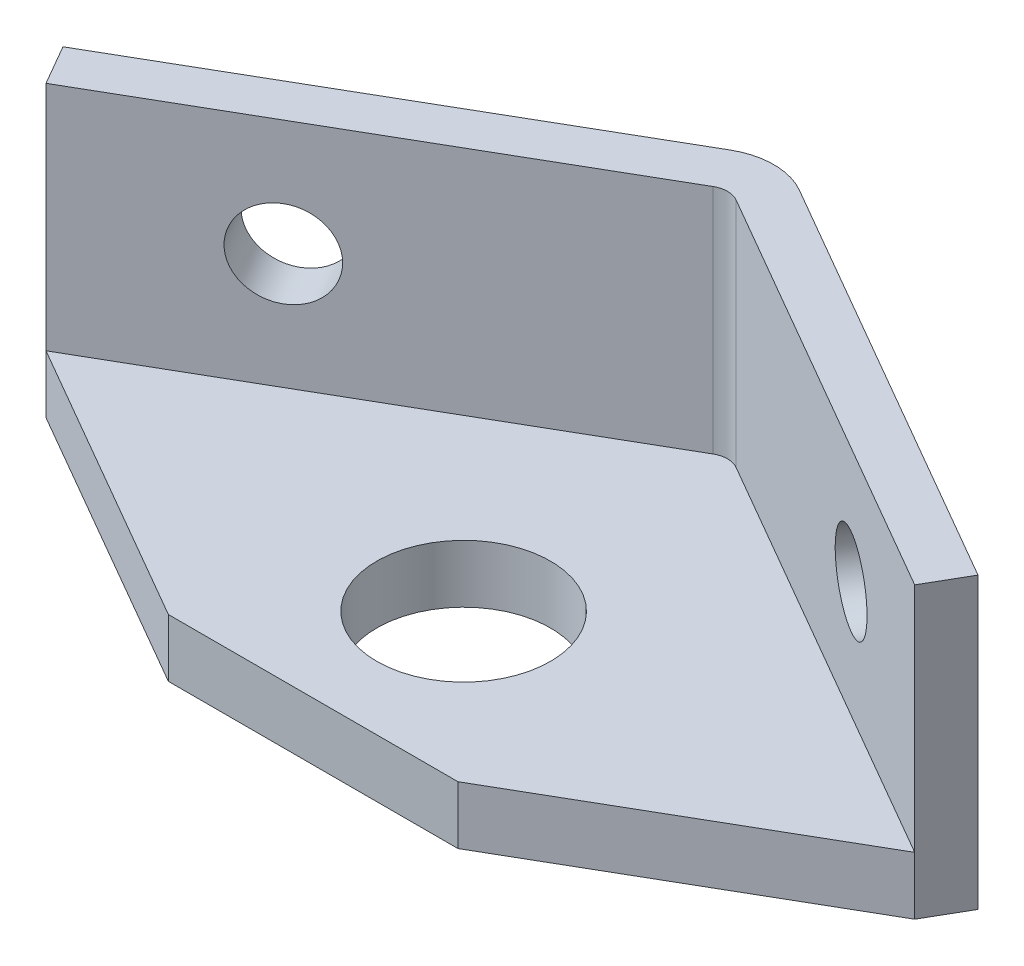
SolidWorks part; units mm, degrees
ref_plane "Plano frontal" through (0, 0, 0) normal (0, 0, 1) x (1, 0, 0)
ref_plane "Plano superior" through (0, 0, 0) normal (0, 1, 0) x (1, 0, 0)
ref_plane "Plano direito" through (0, 0, 0) normal (1, 0, 0) x (0, 0, -1)
sketch "Esboço1" plane through (0, 0, 0) normal (0, 1, 0) x (1, 0, 0)
  line L26 (-2, 45.0333) -> (-75, 2.8868)
  line L27 (-75, 2.8868) -> (0, -40.4145)
  line L28 (0, -40.4145) -> (75, 2.8868)
  line L29 (75, 2.8868) -> (2, 45.0333)
  line L30 (-25, -25.9808) -> (25, -25.9808)
  line L31 (-75, 2.8868) -> (-79, 9.815)
  line L32 (-79, 9.815) -> (-6, 51.9615)
  line L33 (6, 51.9615) -> (79, 9.815)
  line L34 (79, 9.815) -> (75, 2.8868)
  circle A4 centre (0, 0) radius 15
  arc A5 (-6, 51.9615) -> (6, 51.9615) centre (0, 41.5692) cw
  arc A6 (-2, 45.0333) -> (2, 45.0333) centre (0, 41.5692) cw
  point P13 (0, 46.188)
  point P16 (0, 0)
  point P17 (0, -38.5465)
  dimension "D6" = 8
  dimension "D8" = 4
  dimension "D9" = 240
  dimension "D1" = 30
  dimension "D7" = 12
  dimension "D2" = 35
  dimension "D3" = 35
  dimension "D4" = 25
  dimension "D5" = 75
extrude "Ressalto-extrusão4" add sketch "Esboço1" along normal blind 50 contours L26 A6 L29 L34 L33 A5 L32 L31 region at (-39.3296, 0, -25.397)
extrude "Ressalto-extrusão5" add sketch "Esboço1<7>" along normal blind 10 contours A6 L26 L27 L30 L28 L29 A4 region at (0, 0, -43.9073)
sketch "Esboço1<7>" plane through (0, 0, 0) normal (0, 1, 0) x (1, 0, 0) same geometry as "Esboço1"
sketch "Esboço2" plane through (-20, 0, -34.641) normal (0.5, 0, 0.866) x (0.866, 0, -0.5)
  line L0 (-63.5085, 50) -> (-63.5085, 10) construction
  line L1 (20.7846, 50) -> (-63.5085, 50) construction
  circle A0 centre (-33.5085, 30) radius 7.5
  dimension "D1" = 15
  dimension "D2" = 30
  dimension "D3" = 20
extrude "Corte-extrusão1" cut sketch "Esboço2" against normal up to next
sketch "Esboço3" plane through (20, 0, -34.641) normal (-0.5, 0, 0.866) x (0.866, 0, 0.5)
  line L0 (63.5085, 50) -> (63.5085, 10) construction
  line L1 (63.5085, 50) -> (-20.7846, 50) construction
  circle A0 centre (33.5085, 30) radius 7.5
  dimension "D1" = 15
  dimension "D2" = 30
  dimension "D3" = 20
extrude "Corte-extrusão2" cut sketch "Esboço3" against normal up to next
